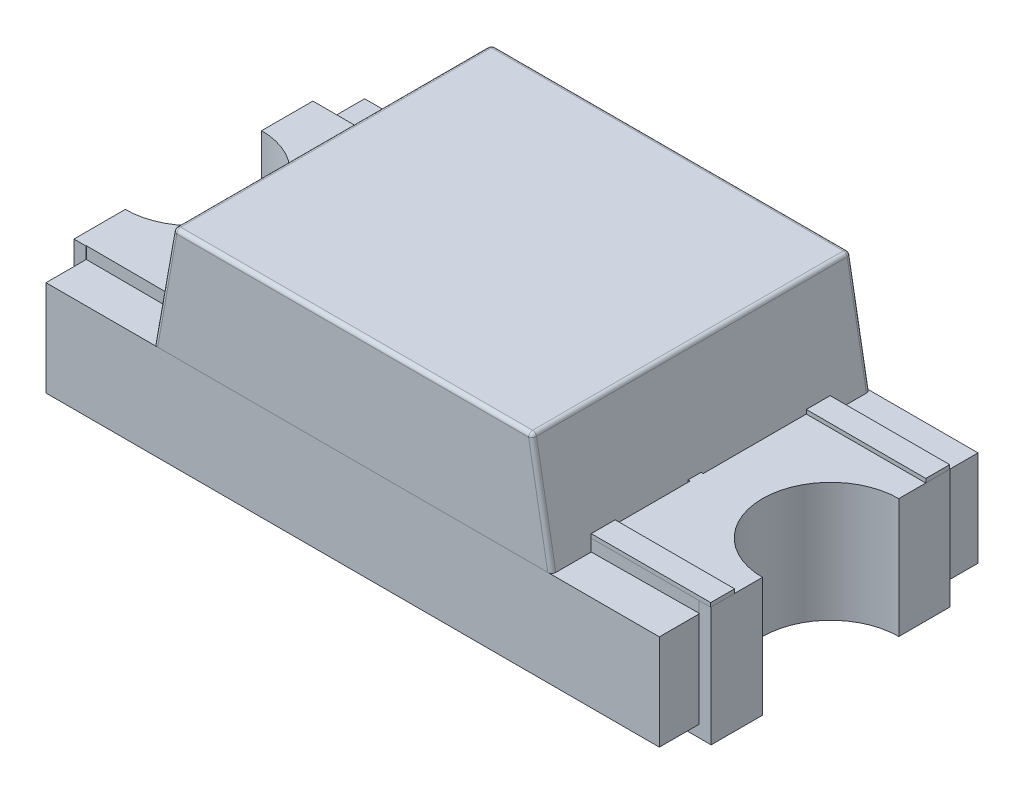
SolidWorks part; units mm, degrees
ref_plane "Спереди" through (0, 0, 0) normal (0, 0, 1) x (1, 0, 0)
ref_plane "Сверху" through (0, 0, 0) normal (0, 1, 0) x (1, 0, 0)
ref_plane "Справа" through (0, 0, 0) normal (1, 0, 0) x (0, 0, -1)
sketch "Эскиз1" plane through (0, 0, 0) normal (0, 1, 0) x (1, 0, 0)
  line L0 (0.375, 0) -> (0.875, 0) construction
  line L1 (-0.375, 0) -> (-0.875, 0) construction
  line L2 (-0.625, -0.45) -> (-0.625, 0.45) construction
  line L3 (0.625, 0.45) -> (0.625, -0.45) construction
  line L4 (-0.8, 0.3) -> (-0.8, 0.1712)
  line L5 (0.8, 0.3) -> (0.5, 0.3)
  line L6 (0.8, 0.3) -> (0.8, -0.3) construction
  line L7 (0.8, -0.3) -> (0.5, -0.3)
  line L8 (0.5, 0.3) -> (0.5, -0.3)
  line L9 (-0.8, 0.3) -> (-0.5, 0.3)
  line L10 (-0.8, 0.3) -> (-0.8, -0.3) construction
  line L11 (-0.8, -0.3) -> (-0.5, -0.3)
  line L12 (-0.5, 0.3) -> (-0.5, -0.3)
  line L13 (-0.8, -0.1712) -> (-0.8, -0.3)
  line L14 (0.8, 0.3) -> (0.8, 0.1712)
  line L15 (0.8, -0.1712) -> (0.8, -0.3)
  arc A0 (-0.8, 0.1712) -> (-0.8, -0.1712) centre (-0.8, 0) cw
  arc A1 (0.8, 0.1712) -> (0.8, -0.1712) centre (0.8, 0) ccw
  point P9 (-0.8, 0.3)
  point P14 (0.8, 0.3)
extrude "Бобышка-Вытянуть1" add sketch "Эскиз1" along normal blind 0.03
sketch "Эскиз2" plane through (0, 0.03, 0) normal (0, 1, 0) x (1, 0, 0)
  line L0 (-0.8, -0.1712) -> (-0.8, -0.3) construction
  line L1 (-0.8, 0.1712) -> (-0.8, 0.3)
  line L2 (-0.8, 0.3) -> (-0.7701, 0.3)
  line L3 (-0.5, 0.3) -> (-0.8, 0.3) construction
  line L5 (-0.8, -0.3) -> (-0.5, -0.3) construction
  line L6 (-0.7701, 0.1978) -> (-0.7701, 0.3)
  line L7 (-0.8, -0.1712) -> (-0.8, -0.3)
  line L8 (-0.8, -0.3) -> (-0.7701, -0.3)
  line L9 (-0.7701, -0.3) -> (-0.7701, -0.1978)
  line L10 (0.8, 0.1712) -> (0.8, 0.3)
  line L11 (0.8, 0.3) -> (0.77, 0.3)
  line L12 (0.8, 0.3) -> (0.5, 0.3) construction
  line L14 (0.5, -0.3) -> (0.8, -0.3) construction
  line L15 (0.77, 0.3) -> (0.77, 0.1977)
  line L16 (0.8, -0.1712) -> (0.8, -0.3)
  line L17 (0.8, -0.3) -> (0.77, -0.3)
  line L18 (0.77, -0.3) -> (0.77, -0.1977)
  arc A0 (-0.8, 0.1712) -> (-0.8, -0.1712) centre (-0.8, 0) cw
  arc A1 (-0.7701, -0.1978) -> (-0.7701, 0.1978) centre (-0.8, 0) ccw
  arc A2 (0.8, 0.1712) -> (0.8, -0.1712) centre (0.8, 0) ccw
  arc A3 (0.8, 0.1712) -> (0.8, -0.1712) centre (0.8, 0) ccw construction
  arc A4 (0.77, 0.1977) -> (0.77, -0.1977) centre (0.8, 0) ccw
extrude "Бобышка-Вытянуть2" add sketch "Эскиз2" along normal blind 0.27
sketch "Эскиз3" plane through (0, 0.03, 0) normal (0, 1, 0) x (1, 0, 0)
  line L0 (-0.7701, -0.3) -> (-0.7701, -0.1978) construction
  line L1 (-0.7701, 0.1978) -> (-0.7701, 0.4)
  line L2 (-0.7701, 0.4) -> (0.77, 0.4)
  line L3 (0.77, 0.4) -> (0.77, 0.1977)
  line L4 (-0.7701, -0.1978) -> (-0.7701, -0.4)
  line L5 (-0.7701, -0.4) -> (0.77, -0.4)
  line L6 (0.77, -0.4) -> (0.77, -0.1977)
  arc A0 (-0.7701, 0.1978) -> (-0.7701, -0.1978) centre (-0.8, 0) cw
  arc A1 (0.77, 0.1977) -> (0.77, -0.1977) centre (0.8, 0) ccw
  arc A2 (0.77, 0.1977) -> (0.77, -0.1977) centre (0.8, 0) ccw construction
  point P15 (-0.7701, 0.4)
  point P19 (-0.7701, -0.4)
extrude "Бобышка-Вытянуть3" add sketch "Эскиз3" along normal blind 0.24 separate body
sketch "Эскиз4" plane through (0, 0.27, 0) normal (0, 1, 0) x (1, 0, 0)
  line L0 (-0.7701, 0.1978) -> (-0.7701, 0.3)
  line L1 (-0.25, 0.25) -> (0.25, 0.25) construction
  line L2 (-0.25, 0.25) -> (-0.25, -0.25) construction
  line L3 (-0.25, -0.25) -> (0.25, -0.25) construction
  line L4 (0.25, 0.25) -> (0.25, -0.25) construction
  line L5 (-0.25, 0.25) -> (0.25, -0.25) construction
  line L6 (-0.25, -0.25) -> (0.25, 0.25) construction
  line L7 (-0.7701, 0.3) -> (-0.5001, 0.3)
  line L8 (-0.5001, 0.3) -> (-0.5001, -0.3) construction
  line L9 (-0.5001, -0.3) -> (-0.7701, -0.2989)
  line L10 (-0.7701, -0.1978) -> (-0.7701, -0.4) construction
  line L11 (-0.7701, -0.2989) -> (-0.7701, -0.1978)
  line L12 (0.77, 0.1977) -> (0.77, 0.2989)
  line L13 (0.77, 0.1977) -> (0.77, 0.4) construction
  line L14 (0.77, 0.2989) -> (0.5, 0.2989)
  line L15 (0.5, 0.2989) -> (0.5, -0.3011) construction
  line L16 (0.5, -0.3011) -> (0.77, -0.2989)
  line L17 (0.77, -0.4) -> (0.77, -0.1977) construction
  line L18 (0.77, -0.2989) -> (0.77, -0.1977)
  line L19 (0.25, 0.25) -> (0.31, 0.25) construction
  line L20 (0.31, 0.25) -> (0.31, -0.0529) construction
  line L21 (0.25, 0.25) -> (0.25, 0.22) construction
  line L22 (0.25, 0.22) -> (0.28, 0.22) construction
  line L23 (0.28, 0.22) -> (0.28, -0.08) construction
  line L24 (0.28, -0.08) -> (0.37, -0.08) construction
  line L25 (0.37, -0.08) -> (0.37, 0.22) construction
  line L26 (0.31, -0.0529) -> (0.34, -0.0529) construction
  line L27 (0.34, -0.0529) -> (0.34, 0.25) construction
  line L28 (0.34, 0.25) -> (0.43, 0.25) construction
  line L29 (0.37, 0.22) -> (0.4, 0.22) construction
  line L30 (0.4, 0.22) -> (0.4, -0.0529) construction
  line L31 (0.4, -0.0529) -> (0.5, -0.0529) construction
  line L32 (0.43, 0.25) -> (0.43, -0.02) construction
  line L33 (0.43, -0.02) -> (0.5, -0.02) construction
  line L34 (-0.5001, 0.25) -> (-0.3781, 0.25) construction
  line L35 (-0.3781, 0.25) -> (-0.3781, -0.1332) construction
  line L36 (-0.3781, -0.1332) -> (-0.3339, -0.1332) construction
  line L37 (-0.3339, -0.1332) -> (-0.3339, -0.25) construction
  line L38 (-0.3339, -0.25) -> (-0.4139, -0.25) construction
  line L39 (-0.4139, -0.25) -> (-0.4139, 0.21) construction
  line L40 (-0.4139, 0.21) -> (-0.5001, 0.21) construction
  line L41 (0.5, 0.2989) -> (0.5, -0.02)
  line L42 (0.5, -0.02) -> (0.43, -0.02)
  line L43 (0.43, -0.02) -> (0.43, 0.25)
  line L44 (0.43, 0.25) -> (0.34, 0.25)
  line L45 (0.34, 0.25) -> (0.34, -0.0529)
  line L46 (0.34, -0.0529) -> (0.31, -0.0529)
  line L47 (0.31, -0.0529) -> (0.31, 0.25)
  line L48 (0.31, 0.25) -> (-0.25, 0.25)
  line L49 (-0.25, 0.25) -> (-0.25, -0.25)
  line L50 (-0.25, -0.25) -> (0.25, -0.25)
  line L51 (0.25, -0.25) -> (0.25, 0.22)
  line L52 (0.25, 0.22) -> (0.28, 0.22)
  line L53 (0.28, 0.22) -> (0.28, -0.08)
  line L54 (0.28, -0.08) -> (0.37, -0.08)
  line L55 (0.37, -0.08) -> (0.37, 0.22)
  line L56 (0.37, 0.22) -> (0.4, 0.22)
  line L57 (0.4, 0.22) -> (0.4, -0.0529)
  line L58 (0.4, -0.0529) -> (0.5, -0.0529)
  line L59 (0.5, -0.0529) -> (0.5, -0.3011)
  line L60 (-0.5001, 0.3) -> (-0.5001, 0.25)
  line L61 (-0.5001, 0.25) -> (-0.3781, 0.25)
  line L62 (-0.3781, 0.25) -> (-0.3781, -0.1332)
  line L63 (-0.3781, -0.1332) -> (-0.3339, -0.1332)
  line L64 (-0.3339, -0.1332) -> (-0.3339, -0.25)
  line L65 (-0.3339, -0.25) -> (-0.4139, -0.25)
  line L66 (-0.4139, -0.25) -> (-0.4139, 0.21)
  line L67 (-0.4139, 0.21) -> (-0.5001, 0.21)
  line L68 (-0.5001, 0.21) -> (-0.5001, -0.3)
  arc A0 (-0.7701, 0.1978) -> (-0.7701, -0.1978) centre (-0.8, 0) cw
  arc A1 (-0.7701, -0.1978) -> (-0.7701, 0.1978) centre (-0.8, 0) ccw construction
  arc A2 (0.77, -0.1977) -> (0.77, 0.1977) centre (0.8, 0) cw
  arc A3 (0.77, 0.1977) -> (0.77, -0.1977) centre (0.8, 0) ccw construction
  point P0 (0, 0)
extrude "Бобышка-Вытянуть4" add sketch "Эскиз4" along normal blind 0.03 separate body
sketch "Эскиз5" plane through (0, 0.27, 0) normal (0, 1, 0) x (1, 0, 0)
  line L2 (-0.7701, -0.4) -> (0.77, -0.4) construction
  line L3 (-0.5, -0.4) -> (0.5, -0.4)
  line L4 (-0.5, -0.4) -> (-0.5, 0.4)
  line L5 (-0.5, 0.4) -> (0.5, 0.4)
  line L6 (0.5, -0.4) -> (0.5, 0.4)
  line L7 (0.77, 0.4) -> (-0.7701, 0.4) construction
sketch "Эскиз7" plane through (0, 0.3, 0) normal (0, 1, 0) x (1, 0, 0)
  line L0 (-0.25, 0) -> (0.25, 0) construction
  line L1 (-0.25, 0.25) -> (0.25, 0.25) construction
  line L2 (-0.25, 0.25) -> (-0.25, -0.25) construction
  line L3 (-0.25, -0.25) -> (0.25, -0.25) construction
  line L4 (0.25, 0.25) -> (0.25, -0.25) construction
sketch "Эскиз9" plane through (0, 0.3, 0) normal (0, 1, 0) x (1, 0, 0)
  circle A0 centre (0, 0) radius 0.04
extrude "Бобышка-Вытянуть5" add sketch "Эскиз9" along normal blind 0.03 separate body
fillet "Скругление1" radius 0.04 1 edges at (0, 0.33, 0.04)
sketch "Эскиз10" plane through (0, 0.3, 0) normal (0, 1, 0) x (1, 0, 0)
  point P4 (-0.3739, -0.1916)
sketch3d "Трехмерный эскиз1"
  line L0 (0, 0.33, 0) -> (0, 0, 0) construction
  line L1 (0, 0.3384, 0) -> (0, 0.2682, 0) construction
ref_plane "Плоскость3" through (0, 0, 0) normal (-0.4561, 0, -0.8899) x (-0.8899, 0, 0.4561)
sketch "Эскиз11" plane through (0, 0, 0) normal (-0.4561, 0, -0.8899) x (-0.8899, 0, 0.4561)
  line L0 (0.4201, 0.3) -> (0.4201, 0.3107)
  line L1 (0, 0.33) -> (0, 0.3393)
  line L2 (0.0107, 0.3492) -> (0.4108, 0.3207)
  arc A0 (0, 0.3393) -> (0.0107, 0.3492) centre (0.01, 0.3393) cw
  arc A1 (0.4201, 0.3107) -> (0.4108, 0.3207) centre (0.4101, 0.3107) ccw
  dimension "D1" = 0.01
sketch "Эскиз14" plane through (0, 0.3, 0) normal (0, 1, 0) x (1, 0, 0)
  line L0 (-0.3739, -0.1916) -> (0, 0) construction
  line L1 (-0.3829, -0.185) -> (-0.374, -0.1804)
  line L2 (-0.3829, -0.185) -> (-0.3738, -0.2028)
  line L3 (-0.374, -0.1804) -> (-0.3649, -0.1982)
  line L4 (-0.3738, -0.2028) -> (-0.3649, -0.1982)
  line L5 (-0.3829, -0.185) -> (-0.3649, -0.1982) construction
  line L6 (-0.374, -0.1804) -> (-0.3738, -0.2028) construction
sweep "По траектории1" add profiles "Эскиз14" path "Эскиз11"
ref_plane "Плоскость4" through (0, 0.55, 0) normal (0, 1, 0) x (1, 0, 0)
sketch "Эскиз17" plane through (0, 0.55, 0) normal (0, 1, 0) x (1, 0, 0)
  line L1 (-0.45, 0.4) -> (0.45, 0.4)
  line L2 (-0.45, 0.4) -> (-0.45, -0.4)
  line L3 (-0.45, -0.4) -> (0.45, -0.4)
  line L4 (0.45, 0.4) -> (0.45, -0.4)
  line L5 (-0.45, 0.4) -> (0.45, -0.4) construction
  line L6 (-0.45, -0.4) -> (0.45, 0.4) construction
  point P0 (0, 0)
loft "По сечениям1" add profiles "Эскиз5", "Эскиз17"
fillet "Скругление2" radius 0.01 8 edges
sketch "Эскиз18" plane through (0, 0.3, 0) normal (0, 1, 0) x (1, 0, 0)
  line L1 (0.5, 0.2989) -> (0.8, 0.2989)
  line L2 (0.5, 0.2989) -> (0.5, 0.2389)
  line L3 (0.5, 0.2389) -> (0.8, 0.2389)
  line L4 (0.8, 0.2989) -> (0.8, 0.2389)
  line L5 (0.5, -0.3011) -> (0.8, -0.3011)
  line L6 (0.5, -0.3011) -> (0.5, -0.2411)
  line L7 (0.5, -0.2411) -> (0.8, -0.2411)
  line L8 (0.8, -0.3011) -> (0.8, -0.2411)
extrude "Бобышка-Вытянуть8" add sketch "Эскиз18" along normal blind 0.01 separate body
combine bodies "Соединить5" operation type add bodies to combine 126 129
combine bodies "Соединить6" operation type add bodies to combine 130 127
